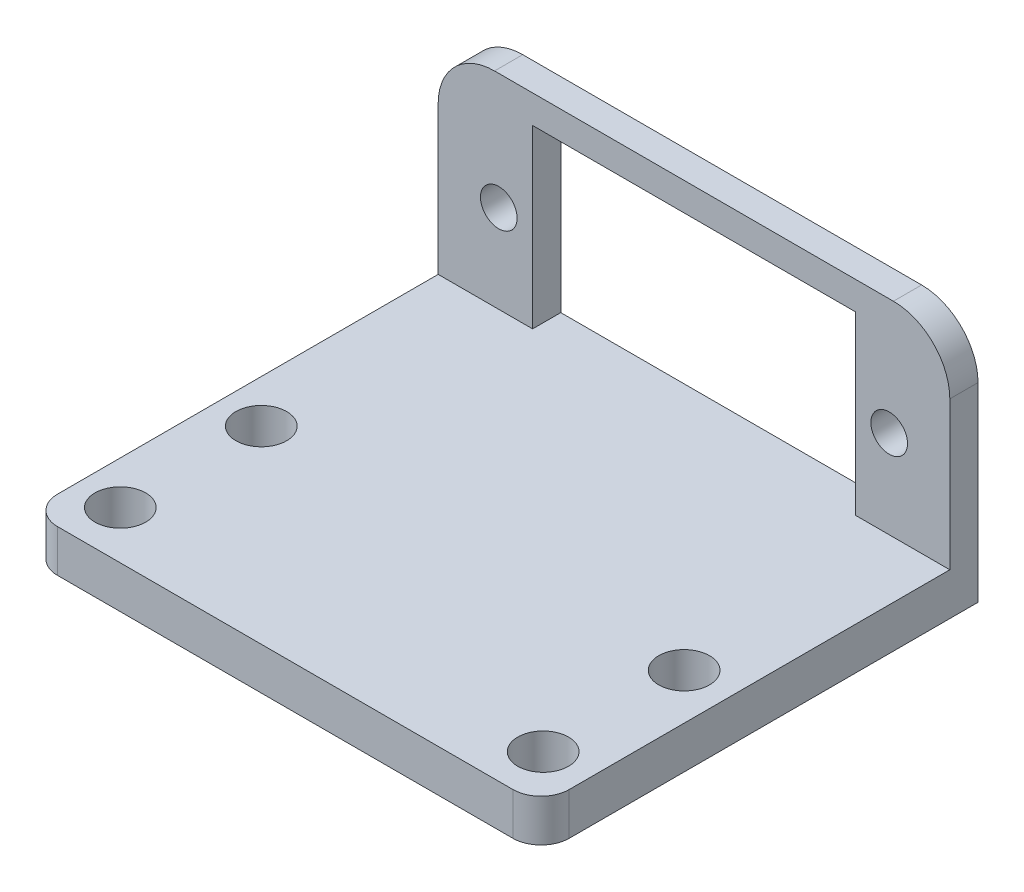
SolidWorks part; units mm, degrees
ref_plane "Front Plane" through (0, 0, 0) normal (0, 0, 1) x (1, 0, 0)
ref_plane "Top Plane" through (0, 0, 0) normal (0, 1, 0) x (1, 0, 0)
ref_plane "Right Plane" through (0, 0, 0) normal (1, 0, 0) x (0, 0, -1)
sketch "Sketch1" plane through (0, 0, 0) normal (0, 0, 1) x (1, 0, 0)
  line L1 (1.5, 2.7805) -> (1.5, 14.8805) construction
  line L2 (-0.5, 8.8305) -> (35.8, 8.8305) construction
  line L3 (-0.5, 17.0805) -> (35.8, 17.0805)
  line L4 (-0.5, 17.0805) -> (-0.5, 0.5805)
  line L5 (-0.5, 0.5805) -> (35.8, 0.5805)
  line L6 (35.8, 17.0805) -> (35.8, 0.5805)
  line L7 (1.5, 14.8805) -> (33.8, 14.8805) construction
  line L8 (17.65, 14.8805) -> (17.65, 8.8305) construction
  line L9 (6.4, 14.8805) -> (6.4, 2.7805) construction
  line L11 (6.2, 15.0805) -> (29.1, 15.0805)
  line L12 (6.2, 15.0805) -> (6.2, 2.5805)
  line L13 (6.2, 2.5805) -> (29.1, 2.5805)
  line L14 (29.1, 15.0805) -> (29.1, 2.5805)
  point P10 (1.5, 8.8305)
  point P21 (17.65, 15.0805)
  point P22 (6.2, 8.8305)
  dimension "D1" = 2
  dimension "D2" = 2.2
  dimension "D3" = 0.2
  dimension "D4" = 0.2
extrude "Boss-Extrude1" add sketch "Sketch1" along normal blind 2
fillet "Fillet1" radius 4 2 edges at (35.8, 17.0805, 1) (-0.5, 17.0805, 1)
sketch "Sketch2" plane through (0, 0, 2) normal (0, 0, 1) x (1, 0, 0)
  point P0 (31.5, 8.8305)
  point P3 (3.8, 8.8305)
hole_wizard "M2 Clearance Hole1" positions "Sketch2" profile "Sketch3" hole size "M2" standard "ANSI Metric" end condition through all
sketch "Sketch3" plane through (31.5, 8.8305, 2) normal (1, 0, 0) x (0, -1, 0)
  line L0 (0, 0) -> (0, 2)
  line L1 (0, 2) -> (1.3, 2)
  line L2 (1.3, 2) -> (1.3, 0)
  line L5 (1.3, 0) -> (0, 0)
  line L11 (0, -6.35) -> (0, 107.95) construction
  dimension "Thru Hole Dia." = 2.6
  dimension "Thru Hole Depth" = 2
sketch "Sketch4" plane through (0, 0, 2) normal (0, 0, 1) x (1, 0, 0)
  line L0 (-0.5, 13.0805) -> (-0.5, 0.5805) construction
  line L1 (-0.5, 2.5805) -> (35.8, 2.5805)
  line L2 (-0.5, 2.5805) -> (-0.5, -0.4195)
  line L3 (-0.5, -0.4195) -> (35.8, -0.4195)
  line L4 (35.8, 2.5805) -> (35.8, -0.4195)
  line L5 (6.2, 2.5805) -> (29.1, 2.5805) construction
  line L6 (35.8, 0.5805) -> (35.8, 13.0805) construction
  dimension "D1" = 3
extrude "Boss-Extrude2" add sketch "Sketch4" along normal blind 29
extrude "Boss-Extrude3" add sketch "Sketch4<2>" against normal up to surface (2 mm away) up to face at (32.8, 8.8305, 0)
sketch "Sketch4<2>" plane through (0, 0, 2) normal (0, 0, 1) x (1, 0, 0) same geometry as "Sketch4"
fillet "Fillet2" radius 2 2 edges at (35.8, 1.0805, 31) (-0.5, 1.0805, 31)
sketch "Sketch5" plane through (0, 2.5805, 0) normal (0, 1, 0) x (1, 0, 0)
  point P0 (2.55, -17.6)
  point P3 (2.55, -27.6)
  point P6 (32.55, -17.6)
  point P9 (32.55, -27.6)
hole_wizard "M3 Clearance Hole1" positions "Sketch5" profile "Sketch6" hole size "M3" standard "ANSI Metric" end condition through all
sketch "Sketch6" plane through (2.55, 2.5805, 17.6) normal (1, 0, 0) x (0, 0, 1)
  line L0 (0, 0) -> (0, 3)
  line L1 (0, 3) -> (1.8, 3)
  line L2 (1.8, 3) -> (1.8, 0)
  line L5 (1.8, 0) -> (0, 0)
  line L11 (0, -6.35) -> (0, 107.95) construction
  dimension "Thru Hole Dia." = 3.6
  dimension "Thru Hole Depth" = 3
